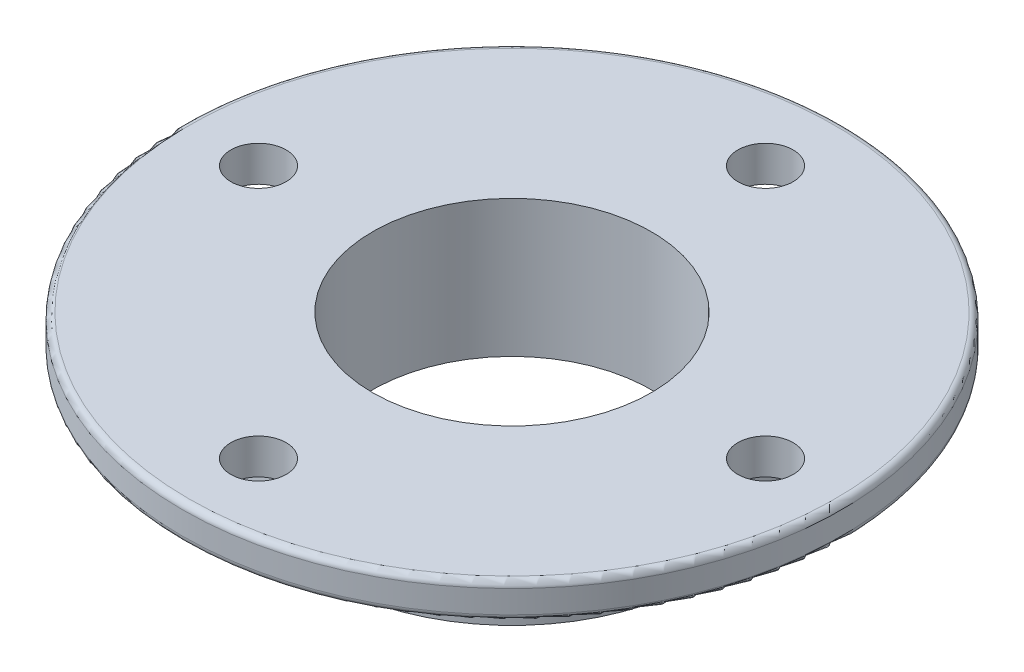
SolidWorks part; units mm, degrees
ref_plane "Front" through (0, 0, 0) normal (0, 0, 1) x (1, 0, 0)
ref_plane "Top" through (0, 0, 0) normal (0, 1, 0) x (1, 0, 0)
ref_plane "Right" through (0, 0, 0) normal (1, 0, 0) x (0, 0, -1)
sketch "Sketch1" plane through (0, 0, 0) normal (0, 1, 0) x (1, 0, 0)
  circle A0 centre (0, 0) radius 5.5
  circle A1 centre (0, 0) radius 7.5
  dimension "D1" = 11
  dimension "D2" = 15
extrude "Boss-Extrude1" add sketch "Sketch1" along normal blind 4
ref_plane "Plane1" through (0, 4, 0) normal (0, 1, 0) x (1, 0, 0)
sketch "Sketch2" plane through (0, 4, 0) normal (0, 1, 0) x (1, 0, 0)
  circle A0 centre (0, 0) radius 13
  circle A1 centre (0, 0) radius 5.5
  circle A2 centre (0, 0) radius 5.5 construction
  dimension "D2" = 26
extrude "Boss-Extrude2" add sketch "Sketch2" along normal blind 1.4
sketch "Sketch3" plane through (0, 5.4, 0) normal (0, 1, 0) x (1, 0, 0)
  line L0 (0, 0) -> (0, 13) construction
  circle A0 centre (0, 0) radius 13 construction
  circle A1 centre (0, 10) radius 1.09
  dimension "D1" = 2.18
  dimension "D2" = 10
extrude "Cut-Extrude1" cut sketch "Sketch3" against normal through all
pattern_circular "CirPattern1" count 4 over 360 about axis through (0, 4, 0) along (0, -1, 0) of "Cut-Extrude1"
fillet "Fillet1" radius 0.25 2 edges at (0, 5.4, 13) (0, 4, 13)
